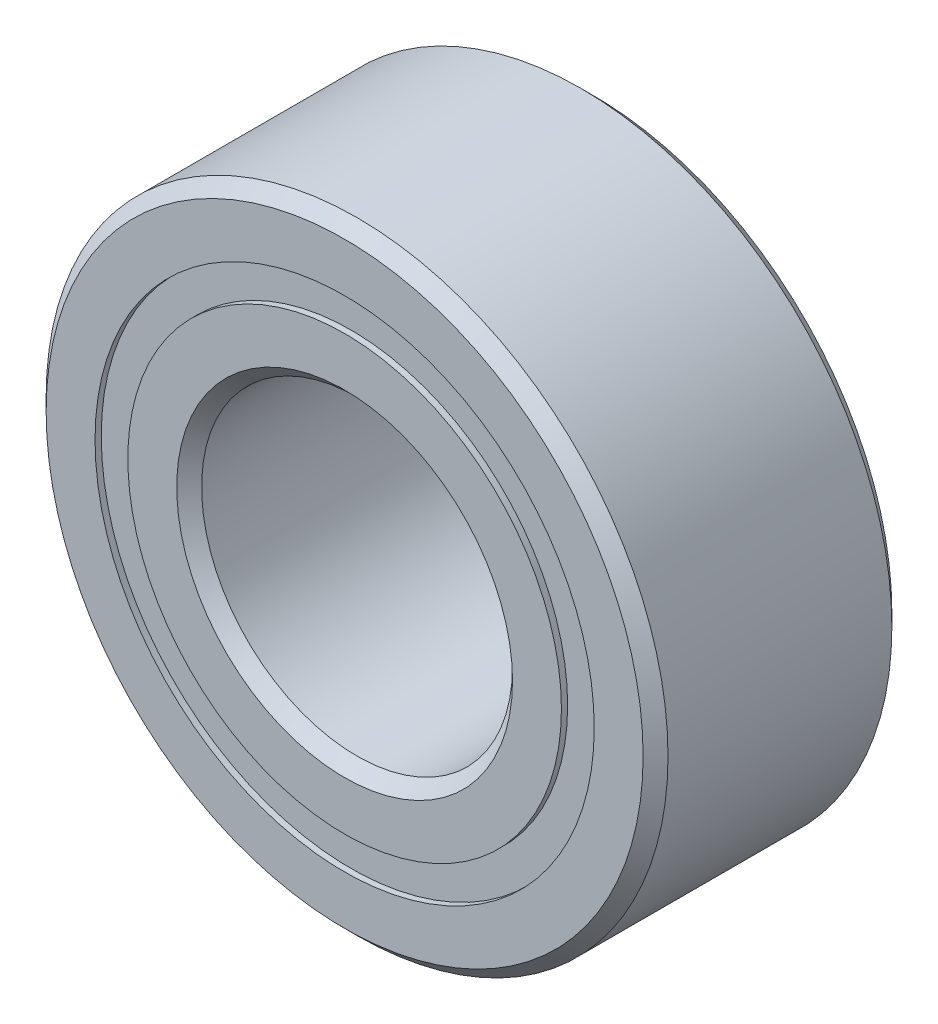
SolidWorks part; units mm, degrees
ref_plane "Front Plane" through (0, 0, 0) normal (0, 0, 1) x (1, 0, 0)
ref_plane "Top Plane" through (0, 0, 0) normal (0, 1, 0) x (1, 0, 0)
ref_plane "Right Plane" through (0, 0, 0) normal (1, 0, 0) x (0, 0, -1)
sketch "Sketch1" plane through (0, 0, 0) normal (1, 0, 0) x (0, 0, -1)
  line L0 (-1.5875, 0) -> (1.5875, 0) construction
  line L1 (0, 3.9688) -> (0, -3.9688) construction
  line L2 (1.4288, 3.9688) -> (-1.4288, 3.9688)
  line L3 (-1.4288, 3.9688) -> (-1.5875, 3.81)
  line L4 (-1.5875, 3.81) -> (-1.5875, 3.1859)
  line L5 (-1.5875, 3.1859) -> (-0.7056, 3.1859)
  line L6 (1.5875, 3.1859) -> (0.7056, 3.1859)
  line L7 (1.5875, 3.81) -> (1.5875, 3.1859)
  line L8 (1.4288, 3.9688) -> (1.5875, 3.81)
  line L9 (0, 3.9688) -> (0, 2.9766) construction
  line L10 (0, 2.9766) -> (0, 1.9844) construction
  arc A0 (-0.7056, 3.1859) -> (0.7056, 3.1859) centre (0, 2.9766) cw
  point P14 (0, 1.9844)
  dimension "Width" = 3.175
  dimension "OD" = 7.9375
  dimension "D1" = 45
  dimension "D2" = 0.1588
  dimension "D3" = 1.4111
  dimension "D4" = 0.2093
revolve "Revolve1" add sketch "Sketch1" angle 360 about L0
sketch "Sketch3" plane through (0, 0, 0) normal (1, 0, 0) x (0, 0, -1)
  line L0 (-0.7056, 2.7672) -> (-1.5875, 2.7672)
  line L1 (-1.5875, 3.81) -> (-1.5875, 3.1859) construction
  line L2 (-1.4288, 3.9688) -> (-1.5875, 3.81) construction
  line L3 (-1.5875, 2.7672) -> (-1.5875, 2.1431)
  line L5 (-1.5875, 2.1431) -> (-1.4288, 1.9844)
  line L6 (-1.4288, 1.9844) -> (1.4288, 1.9844)
  line L7 (1.4288, 3.9688) -> (1.4288, -3.9688) construction
  line L8 (1.4288, 1.9844) -> (1.5875, 2.1431)
  line L9 (1.5875, -3.81) -> (1.5875, 3.81) construction
  line L10 (1.5875, 2.1431) -> (1.5875, 2.7672)
  line L11 (1.5875, 2.7672) -> (0.7056, 2.7672)
  line L12 (0, 3.9688) -> (0, -3.9688) construction
  line L13 (1.4288, 3.9688) -> (1.5875, 3.81) construction
  arc A1 (0.7056, 2.7672) -> (-0.7056, 2.7672) centre (0, 2.9766) cw
  arc A2 (0.7056, 3.1859) -> (-0.7056, 3.1859) centre (0, 2.9766) ccw construction
revolve "Revolve3" add sketch "Sketch3" angle 360 about L0
sketch "Sketch4" plane through (0, 0, 0) normal (1, 0, 0) x (0, 0, -1)
  line L0 (-0.736, 2.9766) -> (0.736, 2.9766)
  arc A2 (-0.736, 2.9766) -> (0.736, 2.9766) centre (0, 2.9766) cw
  arc A3 (0.7056, 3.1859) -> (-0.7056, 3.1859) centre (0, 2.9766) ccw construction
revolve "Revolve4" add sketch "Sketch4" angle 360 about L0
ref_axis "Axis1" through (0, 0, -1.5875) along (0, 0, 1)
pattern_circular "CirPattern1" count 12 every 30 about axis through (0, 0, -1.5875) along (0, 0, 1) of bodies 104
sketch "Sketch5" plane through (0, 0, 0) normal (1, 0, 0) x (0, 0, -1)
  line L0 (-1.5875, 3.1859) -> (-0.7056, 3.1859) construction
  line L1 (-1.5081, 3.1859) -> (-0.736, 3.1859)
  line L2 (-1.5081, 3.1859) -> (-1.5081, 2.7672)
  line L3 (-1.5081, 2.7672) -> (-0.736, 2.7672)
  line L4 (-0.736, 3.1859) -> (-0.736, 2.7672)
  line L5 (-0.7056, 2.7672) -> (-1.5875, 2.7672) construction
  line L6 (1.5875, 3.1859) -> (0.7056, 3.1859) construction
  line L7 (1.5081, 3.1859) -> (0.736, 3.1859)
  line L8 (1.5081, 3.1859) -> (1.5081, 2.7672)
  line L9 (1.5081, 2.7672) -> (0.736, 2.7672)
  line L10 (0.736, 3.1859) -> (0.736, 2.7672)
  line L11 (1.5875, 2.7672) -> (0.7056, 2.7672) construction
  line L12 (-1.4288, 3.9688) -> (-1.5875, 3.81) construction
  point P18 (-1.5081, 3.8894)
revolve "Revolve5" add sketch "Sketch5" angle 360 about L0
equation "\"D2@Sketch1\" = \"Width@Sketch1\"*.05"
equation "\"D3@Sketch1\" = \"Width@Sketch1\"/2.25"
equation "\"D4@Sketch1\" = (((\"OD@Sketch1\"-\"Width@Sketch1\")/2)/3.25)/3.5"
equation "\"D2@CirPattern1\" = 360/\"Balls@CirPattern1\""
